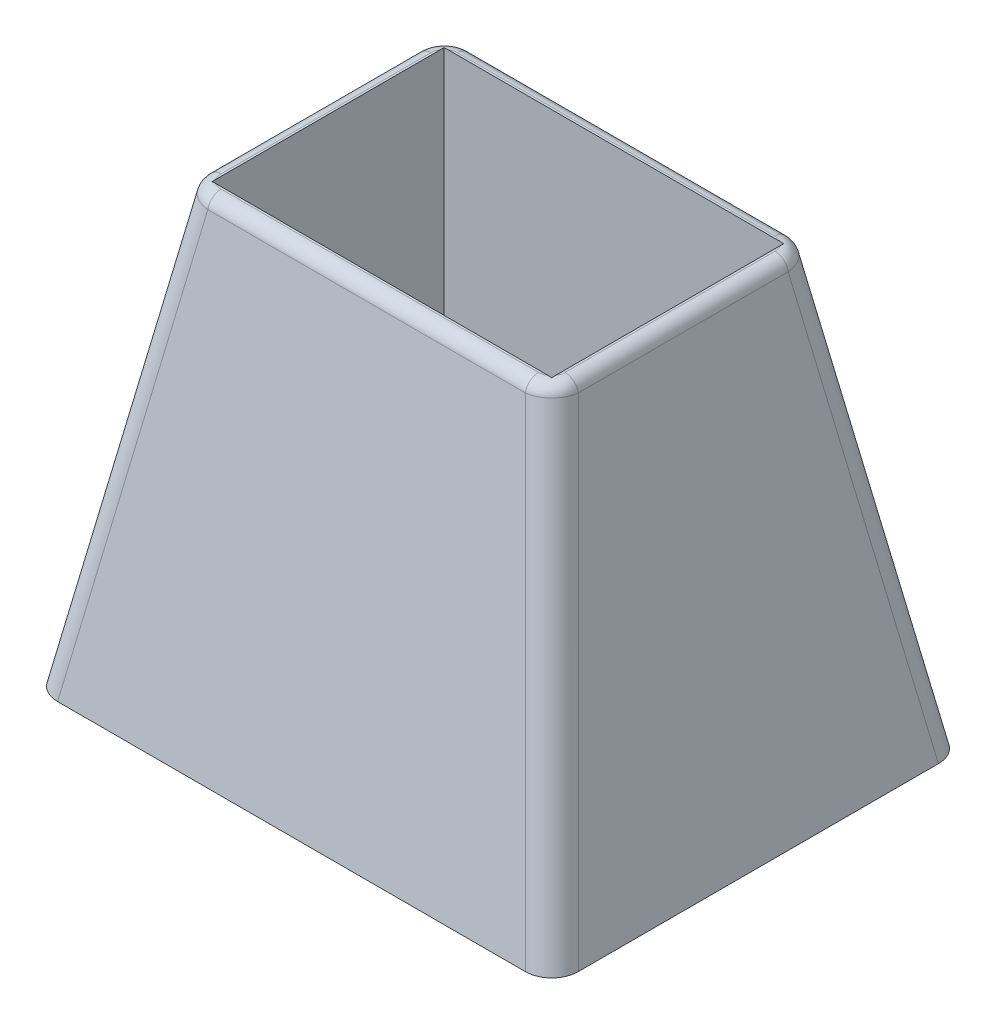
SolidWorks part; units mm, degrees
ref_plane "Front Plane" through (0, 0, 0) normal (0, 0, 1) x (1, 0, 0)
ref_plane "Top Plane" through (0, 0, 0) normal (0, 1, 0) x (1, 0, 0)
ref_plane "Right Plane" through (0, 0, 0) normal (1, 0, 0) x (0, 0, -1)
sketch "Sketch1" plane through (0, 0, 0) normal (0, 1, 0) x (1, 0, 0)
  line L1 (0, 0) -> (54.5, 0)
  line L2 (0, 0) -> (0, -38.5)
  line L3 (0, -38.5) -> (54.5, -38.5)
  line L4 (54.5, 0) -> (54.5, -38.5)
  dimension "D1" = 54.5
  dimension "D2" = 38.5
extrude "Boss-Extrude1" add sketch "Sketch1" against normal blind 65 draft 10 draft outward yes
sketch "Esboço3" plane through (0, 0, 0) normal (0, 1, 0) x (1, 0, 0)
  line L0 (0, -38.5) -> (54.5, -38.5) construction
  line L1 (2, -2) -> (52.5, -2)
  line L2 (2, -2) -> (2, -36.5)
  line L3 (2, -36.5) -> (52.5, -36.5)
  line L4 (52.5, -2) -> (52.5, -36.5)
  line L6 (0, 0) -> (0, -38.5) construction
  dimension "D1" = 50.5
  dimension "D2" = 34.5
  dimension "D3" = 2
  dimension "D4" = 2
extrude "Corte-extrusão1" cut sketch "Esboço3" against normal blind 60
sketch "Esboço4" plane through (0, -60, 0) normal (0, 1, 0) x (1, 0, 0)
  line L0 (2, -2) -> (2, -36.5) construction
  line L1 (52.5, -36.5) -> (52.5, -2) construction
  line L2 (52.5, -2) -> (2, -2) construction
  circle A0 centre (5.3, -5.3) radius 2
  circle A1 centre (49.2, -5.3) radius 2
  dimension "D1" = 4
  dimension "D2" = 4
  dimension "D6" = 3.3
  dimension "D3" = 3.3
  dimension "D4" = 3.3
  dimension "D5" = 3.3
extrude "Corte-extrusão2" cut sketch "Esboço4" against normal through all
fillet "Filete1" radius 4 4 edges at (60.2306, -32.5, 44.2306) (60.2306, -32.5, -5.7306) (-5.7306, -32.5, -5.7306) (-5.7306, -32.5, 44.2306)
fillet "Filete2" radius 2 8 edges at (1.1467, 0, 37.3533) (1.1467, 0, 1.1467) (53.3533, 0, 1.1467) (53.3533, 0, 37.3533) (54.5, 0, 19.25) (27.25, 0, 0) (0, 0, 19.25) (27.25, 0, 38.5)
